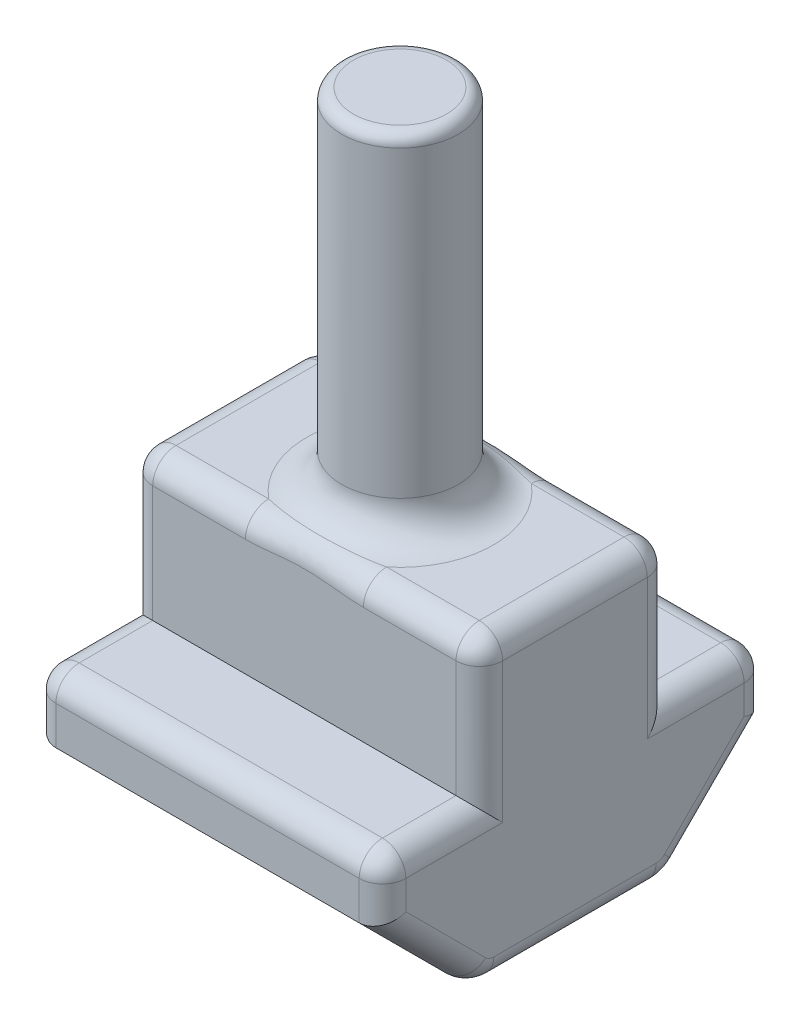
SolidWorks part; units mm, degrees
ref_plane "Front Plane" through (0, 0, 0) normal (0, 0, 1) x (1, 0, 0)
ref_plane "Top Plane" through (0, 0, 0) normal (0, 1, 0) x (1, 0, 0)
ref_plane "Right Plane" through (0, 0, 0) normal (1, 0, 0) x (0, 0, -1)
sketch "Sketch1" plane through (0, 0, 0) normal (1, 0, 0) x (0, 0, -1)
  line L8 (10.9, 33.6) -> (10.9, 27.6)
  line L9 (19.1, 33.6) -> (19.1, 27.6)
  line L13 (10.9, 33.6) -> (19.1, 33.6)
  line L21 (6.75, 27.6) -> (10.9, 27.6)
  line L25 (19.1, 27.6) -> (23.25, 27.6)
  line L26 (19.1, 20.8) -> (10.9, 20.8)
  line L34 (6.75, 24.95) -> (6.75, 27.6)
  line L51 (19.1, 20.8) -> (23.25, 24.95)
  line L52 (6.75, 24.95) -> (10.9, 20.8)
  line L60 (23.25, 27.6) -> (23.25, 24.95)
  point P11 (19.1, 33.6)
  point P12 (10.9, 33.6)
  point P59 (15, 20.8)
  point P70 (15, 20.8)
  point P88 (23.25, 24.95)
  point P90 (6.75, 24.95)
  dimension "D1" = 6
sketch "Sketch9" plane through (0, 0, 0) normal (1, 0, 0) x (0, 0, -1)
  line L0 (10.9, 27.6) -> (19.1, 27.6)
  line L1 (19.1, 27.6) -> (23.25, 27.6)
  line L2 (23.25, 27.6) -> (23.25, 24.95)
  line L3 (23.25, 24.95) -> (19.1, 20.8)
  line L4 (19.1, 20.8) -> (10.9, 20.8)
  line L5 (10.9, 20.8) -> (6.75, 24.95)
  line L6 (6.75, 24.95) -> (6.75, 27.6)
  line L7 (6.75, 27.6) -> (10.9, 27.6)
extrude "Boss-Extrude7" add sketch "Sketch9" along normal blind 15
sketch "Sketch10" plane through (0, 0, 0) normal (1, 0, 0) x (0, 0, -1)
  line L0 (10.9, 27.6) -> (10.9, 33.6)
  line L1 (10.9, 33.6) -> (19.1, 33.6)
  line L2 (19.1, 33.6) -> (19.1, 27.6)
  line L3 (19.1, 27.6) -> (10.9, 27.6)
  dimension "D1" = 6
extrude "Boss-Extrude8" add sketch "Sketch10" along normal blind 15
extrude "Boss-Extrude9" add sketch "Sketch1" along normal blind 15
sketch "Sketch14" plane through (0, 33.6, 0) normal (0, 1, 0) x (1, 0, 0)
  line L0 (0, 19.1) -> (15, 10.9) construction
  line L1 (0, 10.9) -> (15, 19.1) construction
  circle A0 centre (7.5, 15) radius 2.5
  dimension "D1" = 5
extrude "Boss-Extrude10" add sketch "Sketch14" along normal blind 15
fillet "Fillet9" radius 1.5 1 edges at (7.5, 33.6, -12.5)
fillet "Fillet10" radius 0.5 1 edges at (7.5, 48.6, -12.5)
fillet "Fillet11" radius 1.5 2 edges at (7.5, 20.8, -10.9) (7.5, 20.8, -19.1)
fillet "Fillet12" radius 1 2 edges at (7.5, 27.6, -6.75) (7.5, 27.6, -23.25)
fillet "Fillet13" radius 1 13 edges at (15, 30.6, -10.9) (15, 33.6, -15) (15, 30.6, -19.1) (15, 27.6, -20.675) (15, 27.3071, -22.9571) (15, 25.775, -23.25) (15, 23.0947, -21.3947) (15, 20.9142, -19.0527) (15, 20.8, -15) (15, 20.9142, -10.9473) (15, 23.0947, -8.6053) (15, 25.775, -6.75) (15, 27.3071, -7.0429)
fillet "Fillet14" radius 1 13 edges at (0, 23.0947, -8.6053) (0, 20.9142, -10.9473) (0, 20.8, -15) (0, 20.9142, -19.0527) (0, 23.0947, -21.3947) (0, 25.775, -23.25) (0, 27.3071, -22.9571) (0, 27.6, -20.675) (0, 30.6, -19.1) (0, 33.6, -15) (0, 30.6, -10.9) (0, 27.3071, -7.0429) (0, 25.775, -6.75)
fillet "Fillet15" radius 1 6 edges at (14.7071, 33.3071, -11.1929) (0.2929, 33.3071, -11.1929) (14.7071, 33.3071, -18.8071) (0.2929, 33.3071, -18.8071) (7.5, 33.6, -10.9) (7.5, 33.6, -19.1)
